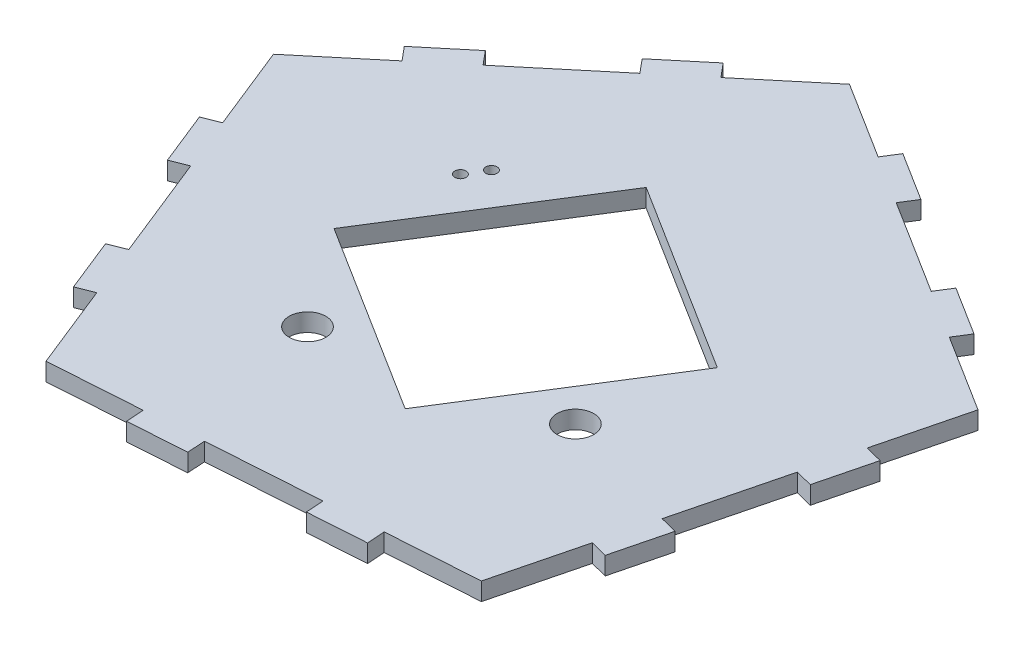
SolidWorks part; units mm, degrees
ref_plane "Front Plane" through (0, 0, 0) normal (0, 0, 1) x (1, 0, 0)
ref_plane "Top Plane" through (0, 0, 0) normal (0, 1, 0) x (1, 0, 0)
ref_plane "Right Plane" through (0, 0, 0) normal (1, 0, 0) x (0, 0, -1)
sketch "Sketch1" plane through (0, 0, 0) normal (0, 1, 0) x (1, 0, 0)
  line L1 (-59.9258, 15.1181) -> (-32.8962, -52.3211)
  line L2 (-32.8962, -52.3211) -> (39.5948, -47.4543)
  line L3 (39.5948, -47.4543) -> (57.3672, 22.9927)
  line L4 (57.3672, 22.9927) -> (-4.14, 61.6646)
  line L5 (-4.14, 61.6646) -> (-59.9258, 15.1181)
  circle A0 centre (0, 0) radius 50 construction
  dimension "D1" = 100
extrude "Boss-Extrude1" add sketch "Sketch1" along normal blind 3.18
ref_axis "Axis" through (0, 3.339, 0) along (0, -1, 0)
sketch "Axis Check" plane through (0, 3.18, 0) normal (0, 1, 0) x (1, 0, 0)
  line L0 (3.3493, -49.8877) -> (-4.14, 61.6646) construction
  line L1 (-32.8962, -52.3211) -> (39.5948, -47.4543) construction
  line L2 (57.3672, 22.9927) -> (-46.411, -18.6015) construction
  line L3 (-59.9258, 15.1181) -> (-32.8962, -52.3211) construction
  line L4 (-32.0329, 38.3913) -> (39.5948, -47.4543) construction
  line L5 (-4.14, 61.6646) -> (-59.9258, 15.1181) construction
  line L6 (-59.9258, 15.1181) -> (48.481, -12.2308) construction
  line L7 (39.5948, -47.4543) -> (57.3672, 22.9927) construction
  line L8 (-32.8962, -52.3211) -> (26.6136, 42.3287) construction
  line L9 (57.3672, 22.9927) -> (-4.14, 61.6646) construction
sketch "Sketch2" plane through (0, 0, 0) normal (0, -1, 0) x (1, 0, 0)
  line L0 (-53.8107, 0.1392) -> (-50.859, -1.0438)
  line L1 (-53.8107, 0.1392) -> (-50.1723, 9.2172)
  line L2 (-50.859, -1.0438) -> (-47.2205, 8.0342)
  line L3 (-50.1723, 9.2172) -> (-47.2205, 8.0342)
  line L4 (-59.9258, -15.1181) -> (-32.8962, 52.3211) construction
  line L5 (-42.6498, 27.9858) -> (-39.0113, 37.0638)
  line L6 (-42.6498, 27.9858) -> (-39.6981, 26.8028)
  line L7 (-39.0113, 37.0638) -> (-36.0596, 35.8808)
  line L8 (-39.6981, 26.8028) -> (-36.0596, 35.8808)
  line L9 (-46.411, 18.6015) -> (-19.2439, 7.7129) construction
  line L10 (-40.8306, 32.5248) -> (-37.8788, 31.3418) construction
  dimension "D1" = 3.18
  dimension "D2" = 9.78
  dimension "D3" = 10.11
extrude "Cut F" [suppressed] cut sketch "Sketch2" against normal through all
sketch "Sketch4" plane through (0, 3.18, 0) normal (0, 1, 0) x (1, 0, 0)
  line L9 (26.6136, 42.3287) -> (-26.6136, -42.3287) construction
  line L10 (57.3672, 22.9927) -> (-4.14, 61.6646) construction
  line L11 (-27.7286, -6.3206) -> (-6.3206, 27.7286)
  line L12 (-27.7286, -6.3206) -> (6.3206, -27.7286)
  line L13 (-6.3206, 27.7286) -> (27.7286, 6.3206)
  line L14 (6.3206, -27.7286) -> (27.7286, 6.3206)
  line L15 (-27.7286, -6.3206) -> (27.7286, 6.3206) construction
  line L16 (-6.3206, 27.7286) -> (6.3206, -27.7286) construction
  line L20 (0, 0) -> (39.0006, -24.5211) construction
  circle A0 centre (-14.9622, -23.7972) radius 3.25
  circle A1 centre (23.7972, -14.9622) radius 3.25
  point P5 (0, 0)
  point P6 (-14.9622, -23.7972)
  dimension "D3" = 6.5
  dimension "D1" = 40.22
  dimension "D2" = 40.22
  dimension "D4" = 8
  dimension "D5" = 8
extrude "Top Cut" cut sketch "Sketch4" against normal blind 10
sketch "Sketch7" plane through (0, 3.18, 0) normal (0, 1, 0) x (1, 0, 0)
  line L0 (0, 0) -> (26.6136, 42.3287) construction
  line L1 (57.3672, 22.9927) -> (-4.14, 61.6646) construction
  line L2 (1.0645, 1.6931) -> (-22.7326, 16.6553) construction
  line L3 (-6.1086, 1.4782) -> (-24.8617, 13.269) construction
  line L5 (-6.3206, 27.7286) -> (-27.7286, -6.3206) construction
  circle A0 centre (-22.7326, 16.6553) radius 1
  circle A1 centre (-24.8617, 13.269) radius 1
  dimension "D5" = 2
  dimension "D1" = 4
  dimension "D2" = 2
  dimension "D3" = 8
  dimension "D4" = 8
extrude "Top Cut 2" cut sketch "Sketch7" against normal through all
sketch "Sketch8" [suppressed] plane through (0, 3.18, 0) normal (0, 1, 0) x (1, 0, 0)
  line L0 (3.3493, -49.8877) -> (-4.14, 61.6646) construction
  line L5 (-32.8962, -52.3211) -> (39.5948, -47.4543) construction
  line L6 (-17.9455, -31.2723) -> (21.9647, -28.5929)
  line L11 (-17.9455, -31.2723) -> (-21.9647, 28.5929)
  line L12 (21.9647, -28.5929) -> (17.9455, 31.2723)
  line L13 (-21.9647, 28.5929) -> (17.9455, 31.2723)
  point P4 (1.4955, -22.2759)
  dimension "D1" = 60
  dimension "D2" = 40
  dimension "D3" = 20
extrude "Bottom Cut" [suppressed] cut sketch "Sketch8" against normal blind 10
sketch "Sketch9" [suppressed] plane through (0, 3.18, 0) normal (0, 1, 0) x (1, 0, 0)
  line L0 (19.9551, 1.3397) -> (-19.9551, -1.3397) construction
  line L1 (21.9647, -28.5929) -> (17.9455, 31.2723) construction
  line L2 (-21.9647, 28.5929) -> (-17.9455, -31.2723) construction
  line L3 (-19.9551, -1.3397) -> (-44.4689, -2.9855) construction
  line L4 (19.9551, 1.3397) -> (42.6839, 2.8657) construction
  line L5 (-32.8962, -52.3211) -> (39.5948, -47.4543) construction
  line L6 (-29.6051, -6.8886) -> (-32.3788, -7.0748)
  line L7 (-29.6051, -6.8886) -> (-30.2602, 2.8694)
  line L8 (-30.2602, 2.8694) -> (-33.0339, 2.6832)
  line L9 (-32.3788, -7.0748) -> (-33.0339, 2.6832)
  line L10 (-29.6051, -6.8886) -> (-33.0339, 2.6832) construction
  line L11 (-30.2602, 2.8694) -> (-32.3788, -7.0748) construction
  line L12 (33.0339, -2.6832) -> (30.2602, -2.8694)
  line L13 (33.0339, -2.6832) -> (32.3788, 7.0748)
  line L14 (32.3788, 7.0748) -> (29.6051, 6.8886)
  line L15 (30.2602, -2.8694) -> (29.6051, 6.8886)
  line L16 (33.0339, -2.6832) -> (29.6051, 6.8886) construction
  line L17 (32.3788, 7.0748) -> (30.2602, -2.8694) construction
  line L18 (-32.8962, -52.3211) -> (39.5948, -47.4543) construction
  point P6 (-31.3195, -2.1027)
  point P13 (31.3195, 2.1027)
  dimension "D1" = 9.78
  dimension "D4" = 9.78
  dimension "D5" = 10
  dimension "D6" = 10
  dimension "D2" = 2.78
  dimension "D3" = 2.78
extrude "Battery Holder Cut" [suppressed] cut sketch "Sketch9" against normal blind 3.18
sketch "Sketch3" plane through (0, 3.18, 0) normal (0, 1, 0) x (1, 0, 0)
  line L0 (0, 0) -> (-40.9819, 49.1167) construction
  line L1 (-49.5112, 27.9494) -> (-45.4366, 23.066)
  line L3 (-45.4366, 23.066) -> (-37.5894, 29.6135)
  line L4 (-41.664, 34.4969) -> (-37.5894, 29.6135)
  line L5 (-4.14, 61.6646) -> (-59.9258, 15.1181) construction
  line L6 (-71.9961, 5.0469) -> (-69.9588, 2.6052)
  line L7 (-71.9961, 5.0469) -> (-47.4739, 25.5077)
  line L14 (-26.4764, 47.1691) -> (-22.4018, 42.2857)
  line L16 (-22.4018, 42.2857) -> (-14.5546, 48.8333)
  line L17 (-18.6292, 53.7166) -> (-14.5546, 48.8333)
  line L18 (-42.539, 27.5695) -> (-41.513, 26.3398) construction
  line L19 (-49.5112, 27.9494) -> (-41.664, 34.4969)
  line L21 (-26.4764, 47.1691) -> (-18.6292, 53.7166)
  line L22 (-16.5919, 51.275) -> (4.7866, 69.1127)
  line L23 (-39.6267, 32.0552) -> (-24.4391, 44.7274)
  line M18 (-4.14, 61.6646) -> (-59.9258, 15.1181)
  dimension "D1" = 3.18
  dimension "D2" = 10.22
  dimension "D3" = 9.89
  dimension "D4" = 100
extrude "Extrude M" add sketch "Sketch3" against normal up to surface (3.18 mm away) contours L21 L14 L7 L17 | L19 L1 L4 M18 region at (-44.5689, 3.18, -30.0023) region at (-21.5341, 3.18, -49.222) up to face at (-22.7326, 0, -15.6553)
pattern_circular "Circle F" [suppressed] count 5 over 360 about axis through (0, 3.339, 0) along (0, -1, 0) of bodies 173
pattern_circular "Circle M" count 5 over 360 about axis through (0, 3.339, 0) along (0, -1, 0) of "Extrude M"
pattern_circular "Circle Side F" [suppressed] count 5 over 360 about axis through (0, 3.339, 0) along (0, -1, 0) of bodies 173
pattern_circular "Circle Side M" [suppressed] count 5 over 360 about axis through (0, 3.339, 0) along (0, -1, 0) of bodies 168
equation "\"kerf\"= .22mm"
equation "\"tabWidthF\"= 10 - \"kerf\""
equation "\"tabThickness\"= 3.18"
equation "\"D1@Sketch2\"=\"tabThickness\""
equation "\"tabWidthM\"= 10 + \"kerf\""
equation "\"halfkerf\"= \"kerf\" / 2.00mm"
equation "\"D1@Sketch9\"=\"tabWidthF\""
equation "\"D4@Sketch9\"=\"tabWidthF\""
equation "\"D1@Battery Holder Cut\" = \"tabThickness\""
equation "\"tabLength\" = \"kerf\" + 12"
